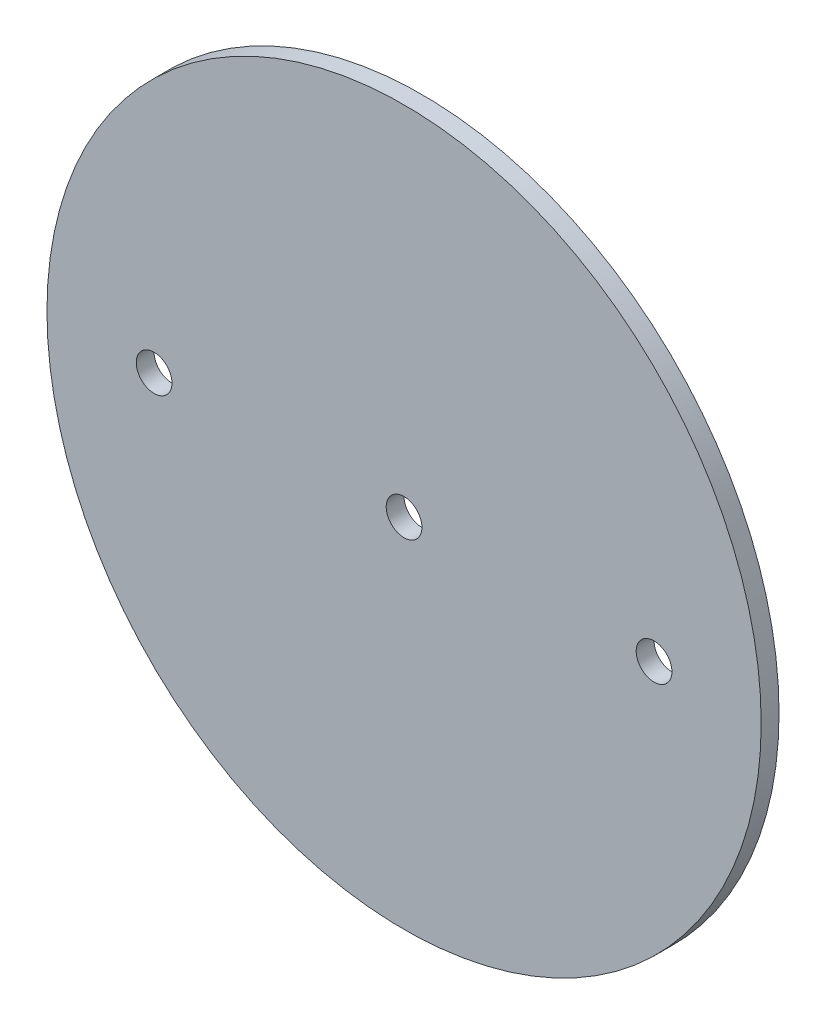
SolidWorks part; units mm, degrees
ref_plane "Front Plane" through (0, 0, 0) normal (0, 0, 1) x (1, 0, 0)
ref_plane "Top Plane" through (0, 0, 0) normal (0, 1, 0) x (1, 0, 0)
ref_plane "Right Plane" through (0, 0, 0) normal (1, 0, 0) x (0, 0, -1)
sketch "Sketch1" plane through (0, 0, 0) normal (0, 0, 1) x (1, 0, 0)
  circle A0 centre (0, 0) radius 63.5
  dimension "D1" = 127
extrude "Boss-Extrude1" add sketch "Sketch1" along normal mid plane 3.175
sketch "Sketch2" plane through (0, 0, 1.5875) normal (0, 0, 1) x (1, 0, 0)
  line L0 (-1000, 0) -> (49000, 0) construction
  point P1 (0, 0)
  point P4 (44.45, 0)
  point P5 (-44.45, 0)
  dimension "D1" = 44.45
  dimension "D2" = 88.9
hole_wizard "1/4 (0.25) Diameter Hole1" positions "Sketch2" profile "Sketch3" hole size "1/4" standard "ANSI Inch" end condition through all
sketch "Sketch3" plane through (-44.45, 0, 1.5875) normal (1, 0, 0) x (0, -1, 0)
  line L0 (0, 0) -> (0, 3.175)
  line L1 (0, 3.175) -> (3.175, 3.175)
  line L2 (3.175, 3.175) -> (3.175, 0)
  line L5 (3.175, 0) -> (0, 0)
  line L11 (0, -6.35) -> (0, 107.95) construction
  dimension "Thru Hole Dia." = 6.35
  dimension "Thru Hole Depth" = 3.175
equation "\"AIRFRAME_OD\"= 5.15in"
equation "\"AIRFRAME_ID\"= 5.00in"
equation "\"FLAT_T\"= 0.125in"
equation "\"NOSE_EXP_L\"= 27in"
equation "\"NOSE_SHOULDER_L\"= 5in"
equation "\"MAIN_L\"= 30in"
equation "\"RECO_COUP_L\"= 10in"
equation "\"RECO_SWITCH_L\"= 2in"
equation "\"DROGUE_L\"= 20in"
equation "\"ATS_FORE_COUP_L\"= 5.5in"
equation "\"ATS_AFT_COUP_L\"= 4.5in"
equation "\"LOWER_L\"= 30in"
equation "\"FIN_N\"= 4"
equation "\"CR_AFT_X\"= 0.5in"
equation "\"CR_FORE_X\"= 9.25in"
equation "\"FIN_ROOT\"= 5in"
equation "\"FIN_X\"= 0.75in"
equation "\"MOTOR_OD\"= 3.091in"
equation "\"MOTOR_ID\"= 3.00in"
equation "\"COUPLER_OD\"= 4.998in"
equation "\"COUPLER_ID\"= 4.88in"
equation "\"D1@Sketch1\"=\"AIRFRAME_ID\""
equation "\"D1@Boss-Extrude1\"=\"FLAT_T\""
equation "\"RECO_ROD_X\"= 3.5in"
equation "\"ATS_ROD_X\"= 3in"
equation "\"D1@Sketch2\"=\"RECO_ROD_X\"*0.5"
equation "\"D2@Sketch2\"=\"RECO_ROD_X\""
equation "\"MOTOR_L\"= 14in"
equation "\"MOTOR_LOWER_X\"= 2in"
